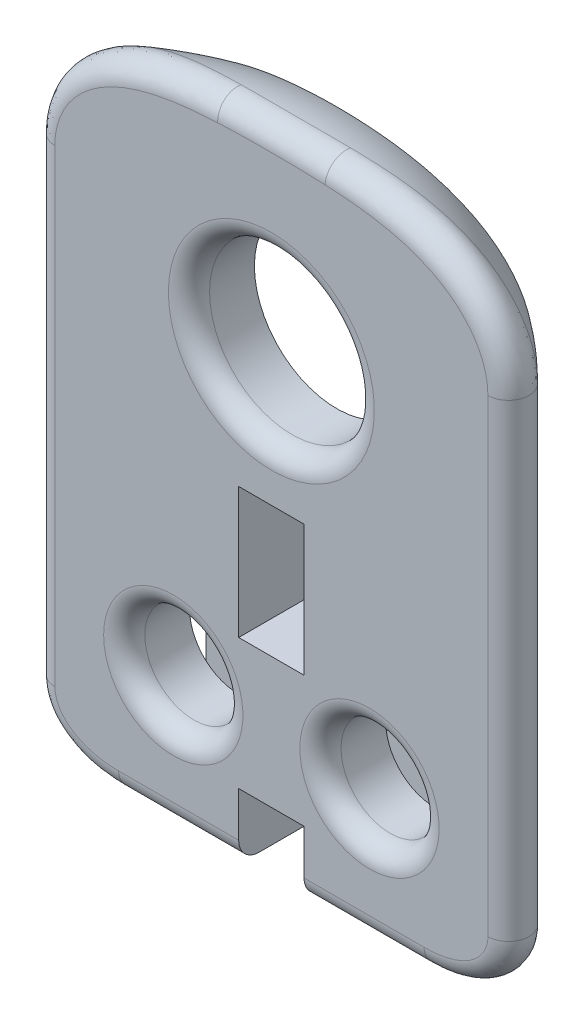
SolidWorks part; units mm, degrees
ref_plane "Front Plane" through (0, 0, 0) normal (0, 0, 1) x (1, 0, 0)
ref_plane "Top Plane" through (0, 0, 0) normal (0, 1, 0) x (1, 0, 0)
ref_plane "Right Plane" through (0, 0, 0) normal (1, 0, 0) x (0, 0, -1)
sketch "Sketch1" plane through (0, 0, 0) normal (0, 0, 1) x (1, 0, 0)
  line L0 (8.89, 6.35) -> (8.89, 0) construction
  line L1 (0, 0) -> (17.78, 0)
  line L2 (0, 0) -> (0, 6.35)
  line L3 (0, 6.35) -> (17.78, 6.35) construction
  line L4 (17.78, 0) -> (17.78, 6.35)
  line L5 (6.5087, 3.175) -> (8.89, 3.175) construction
  line L6 (8.89, 3.175) -> (11.2712, 3.175) construction
  line L7 (0, 6.35) -> (0, 15.875)
  line L8 (0, 15.875) -> (17.78, 15.875)
  line L9 (17.78, 15.875) -> (17.78, 6.35)
  circle A0 centre (6.5087, 3.175) radius 1.1906
  circle A1 centre (11.2712, 3.175) radius 1.1906
  dimension "D4" = 2.3813
  dimension "D1" = 6.35
  dimension "D2" = 17.78
  dimension "D3" = 2.3813
  dimension "D5" = 9.525
extrude "Boss-Extrude1" add sketch "Sketch1" along normal blind 1.5875
fillet "Fillet1" radius 0.5 2 edges at (12.4619, 3.175, 1.5875) (7.6994, 3.175, 1.5875)
sketch "Sketch7" plane through (0, 15.875, 0) normal (0, 1, 0) x (1, 0, 0)
  line L0 (8.89, -1.5875) -> (8.89, -11.1125) construction
  line L2 (17.78, -1.5875) -> (0, -1.5875) construction
  line L3 (-8.0435, 9.8678) -> (25.1044, 9.8678)
  line L4 (-8.0435, 9.8678) -> (-8.0435, -21.7361)
  line L5 (-8.0435, -21.7361) -> (25.1044, -21.7361)
  line L6 (25.1044, 9.8678) -> (25.1044, -21.7361)
  circle A0 centre (8.89, -6.35) radius 7.9375
  dimension "D1" = 15.875
  dimension "D2" = 9.525
extrude "Cut-Extrude2" cut sketch "Sketch7" against normal through all
sketch "Sketch3" plane through (0, 15.875, 0) normal (0, 1, 0) x (1, 0, 0)
  line L0 (8.89, 0) -> (8.89, -1.5875) construction
  line L1 (15.24, -1.5875) -> (2.54, -1.5875) construction
  line L3 (10.4775, 0) -> (7.3025, 0)
  line L4 (7.3025, 0) -> (7.3025, 1.5875)
  line L5 (7.3025, 1.5875) -> (10.4775, 1.5875)
  line L6 (8.89, 1.5875) -> (8.89, 0) construction
  line L7 (10.4775, 0) -> (10.4775, 1.5875)
  line L10 (13.6525, 0) -> (4.1275, 0) construction
  dimension "D1" = 1.5875
  dimension "D2" = 1.5875
extrude "Boss-Extrude3" add sketch "Sketch3" against normal through all
sketch "Sketch5" plane through (0, 0, -1.5875) normal (0, 0, -1) x (-1, 0, 0)
  line L0 (-8.89, 15.875) -> (-8.89, 0) construction
  line L1 (-10.4775, 15.875) -> (-7.3025, 15.875) construction
  line L2 (-10.4775, 0) -> (-7.3025, 0) construction
  line L3 (-8.89, 3.175) -> (-12.065, 3.175) construction
  line L4 (-5.715, 4.7625) -> (-5.715, 1.5875)
  line L5 (-12.065, 4.7625) -> (-10.4775, 4.7625)
  line L6 (-12.065, 4.7625) -> (-12.065, 1.5875)
  line L7 (-12.065, 1.5875) -> (-10.4775, 1.5875)
  line L8 (-10.4775, 2.2876) -> (-10.4775, 0) construction
  line L9 (-10.4775, 4.7625) -> (-10.4775, 1.5875)
  line L10 (-10.4775, 0) -> (-10.4775, 15.875) construction
  line L11 (-7.3025, 4.7625) -> (-7.3025, 1.5875)
  line L12 (-7.3025, 0) -> (-7.3025, 15.875) construction
  line L13 (-7.3025, 4.7625) -> (-5.715, 4.7625)
  line L14 (-7.3025, 1.5875) -> (-5.715, 1.5875)
  line L15 (-8.89, 3.175) -> (-6.5088, 3.175) construction
  point P13 (-8.89, 1.5875)
  point P14 (-8.89, 4.7625)
  dimension "D1" = 3.175
  dimension "D2" = 1.5875
extrude "Boss-Extrude4" add sketch "Sketch5" against normal up to surface (1.5875 mm away) up to face at (11.8666, 5.175, 0)
sketch "Sketch8" plane through (0, 0, 1.5875) normal (0, 0, 1) x (1, 0, 0)
  line L0 (8.89, 0) -> (8.89, 6.35) construction
  line L1 (2.54, 0) -> (15.24, 0) construction
  line L2 (10.0806, 3.175) -> (8.89, 3.175) construction
  line L3 (8.0962, 6.35) -> (8.0962, 7.9375)
  line L4 (8.0962, 0) -> (9.6837, 0)
  line L5 (8.0962, 0) -> (8.0962, 1.5875)
  line L6 (8.0962, 1.5875) -> (9.6837, 1.5875)
  line L7 (9.6837, 0) -> (9.6837, 1.5875)
  line L8 (8.0962, 6.35) -> (9.6837, 6.35) construction
  line L9 (8.0962, 6.35) -> (8.0962, 4.7625)
  line L10 (8.0962, 4.7625) -> (9.6837, 4.7625)
  line L11 (9.6837, 6.35) -> (9.6837, 4.7625)
  line L12 (8.0962, 7.9375) -> (9.6837, 7.9375)
  line L13 (9.6837, 7.9375) -> (9.6837, 6.35)
  arc A0 (12.065, 4.0624) -> (12.065, 2.2876) centre (11.2712, 3.175) ccw construction
  dimension "D1" = 1.5875
  dimension "D2" = 1.5875
extrude "Cut-Extrude3" cut sketch "Sketch8" against normal blind 1.5875
sketch "Sketch10" plane through (0, 0, -1.5875) normal (0, 0, -1) x (-1, 0, 0)
  line L1 (-13.6525, 17.2239) -> (-4.1275, 17.2239)
  line L2 (-13.6525, 17.2239) -> (-13.6525, 6.35)
  line L3 (-13.6525, 6.35) -> (-4.1275, 6.35)
  line L4 (-4.1275, 17.2239) -> (-4.1275, 6.35)
  line L5 (-10.4775, 4.7625) -> (-8.89, 6.35) construction
  line L6 (-8.89, 6.35) -> (-7.3025, 4.7625) construction
  line L7 (-10.4775, 1.5875) -> (-8.89, 0) construction
  line L8 (-10.4775, 0) -> (-7.3025, 0) construction
  line L9 (-8.89, 0) -> (-7.3025, 1.5875) construction
  line L10 (-4.1275, 0) -> (-4.1275, 15.875) construction
  line L12 (-13.6525, 15.875) -> (-13.6525, 0) construction
extrude "Cut-Extrude8" cut sketch "Sketch10" against normal up to surface (1.5875 mm away) up to face at (11.7872, 4.445, 0)
fillet "Fillet2" radius 1.5 2 edges at (3.2773, 0, 0.7373) (14.5027, 0, 0.7373)
sketch "Sketch11" plane through (0, 0, 0) normal (0, 0, -1) x (-1, 0, 0)
  line L0 (-8.89, 0) -> (-8.89, 11.175) construction
  line L1 (-10.4775, 0) -> (-7.3025, 0) construction
  line L3 (-12.065, 3.175) -> (-5.715, 3.175) construction
  line L4 (-12.065, 4.7625) -> (-12.065, 1.5875) construction
  line L5 (-5.715, 1.5875) -> (-5.715, 4.7625) construction
  circle A0 centre (-8.89, 11.175) radius 2
  dimension "D1" = 4
  dimension "D2" = 8
extrude "Cut-Extrude9" cut sketch "Sketch11" against normal through all
fillet "Fillet5" radius 0.5 1 edges at (6.89, 11.175, 1.5875)
fillet "Fillet6" radius 3 2 edges at (3.2773, 15.875, 0.7373) (14.5027, 15.875, 0.7373)
fillet "Fillet4" radius 0.5 9 edges at (2.8242, 0.7091, 1.5875) (6.3275, 0, 1.5875) (11.4525, 0, 1.5875) (14.692, 0.4476, 1.5875) (15.24, 7.1875, 1.5875) (2.54, 7.1875, 1.5875) (8.89, 15.875, 1.5875) (3.9622, 15.1838, 1.5875) (14.6797, 14.4403, 1.5875)
